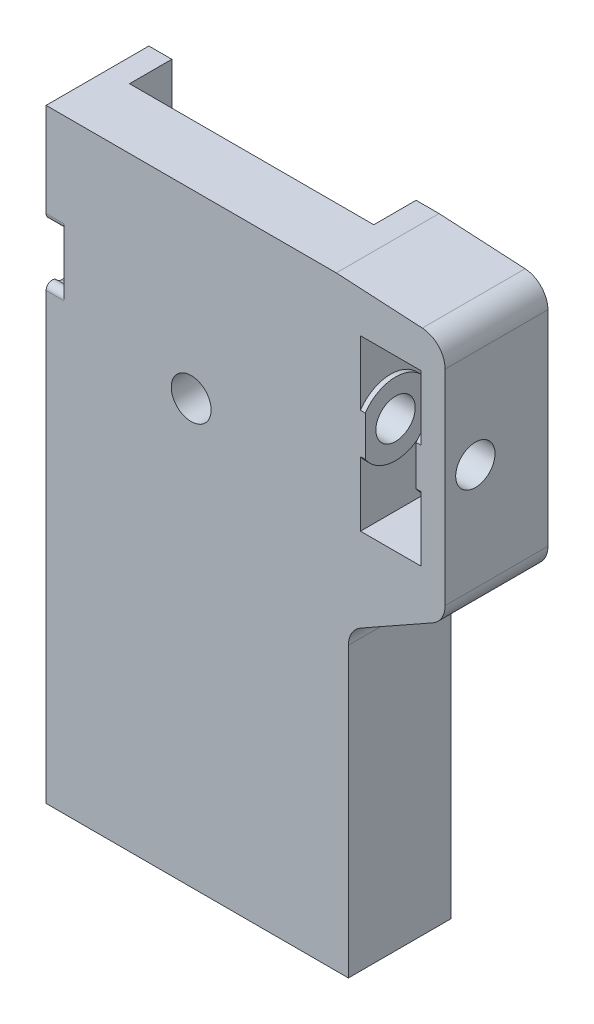
SolidWorks part; units mm, degrees
material "ABS"
ref_plane "前视基准面" through (0, 0, 0) normal (0, 0, 1) x (1, 0, 0)
ref_plane "上视基准面" through (0, 0, 0) normal (0, 1, 0) x (1, 0, 0)
ref_plane "右视基准面" through (0, 0, 0) normal (1, 0, 0) x (0, 0, -1)
other "Configuration Table"
sketch "草图1" plane through (0, 0, 0) normal (0, 0, 1) x (1, 0, 0)
  line L0 (33, 49.5) -> (24, 50)
  line L1 (24, 50) -> (0, 50)
  line L2 (0, 50) -> (0, 0)
  line L5 (33, 29.5) -> (33, 49.5)
  line L6 (26, 32.5) -> (31, 32.5)
  line L7 (26, 46.5) -> (26, 32.5)
  line L12 (31, 46.5) -> (26, 46.5)
  line L17 (31, 32.5) -> (31, 46.5)
  line L18 (0, 0) -> (25, 0)
  line L20 (25, 0) -> (33, 29.5) construction
  line L24 (0, 0) -> (25, 0)
  line L25 (33, 29.5) -> (33, 49.5)
  line L26 (33, 49.5) -> (24, 50)
  line L27 (33, 29.5) -> (25, 25)
  line L28 (25, 25) -> (25, 0)
  circle A0 centre (12, 35) radius 1.65
  dimension "D5" = 3.3
  dimension "D6" = 12
  dimension "D7" = 15
  dimension "D2" = 50
  dimension "D3" = 90
  dimension "D4" = 29.5
  dimension "D8" = 3.5
  dimension "D9" = 26
  dimension "D10" = 5
  dimension "D11" = 14
  dimension "D12" = 25
  dimension "D13" = 33
  dimension "D14" = 4.5
  dimension "D15" = 20
  dimension "D16" = 24
  dimension "D17" = 5
extrude "凸台-拉伸1" add sketch "草图1" against normal blind 8.5 contours L18 L20 L5 L0 L1 L2 A0 L17 L6 L7 L12 region at (13.8498, 25.9744, 0)
sketch "草图2" plane through (0, 50, 0) normal (0, 1, 0) x (1, 0, 0)
  line L0 (24, 8.5) -> (0, 8.5) construction
  line L1 (1.9, 8.5) -> (22.1, 8.5)
  line L2 (1.9, 8.5) -> (1.9, 5)
  line L3 (1.9, 5) -> (22.1, 5)
  line L4 (22.1, 8.5) -> (22.1, 5)
  line L5 (0, 8.5) -> (0, 0) construction
  dimension "D1" = 1.9
  dimension "D2" = 20.2
  dimension "D3" = 3.5
extrude "切除-拉伸1" cut sketch "草图2" against normal through all
sketch "草图3" plane through (33, 0, 0) normal (1, 0, 0) x (0, 0, -1)
  line L0 (0, 29.5) -> (0, 49.5) construction
  circle A0 centre (2.5, 39.5) radius 1.625
  dimension "D1" = 3.25
  dimension "D2" = 2.5
  dimension "D3" = 7
extrude "切除-拉伸2" cut sketch "草图3" against normal through all
sketch "草图6" plane through (31, 0, 0) normal (-1, 0, 0) x (0, 0, 1)
  line L0 (0, 32.5) -> (0, 46.5) construction
  line L1 (0, 37.8417) -> (0, 41.1583)
  circle A0 centre (-2.5, 39.5) radius 1.625 construction
  circle A1 centre (-2.5, 39.5) radius 1.625
  arc A2 (0, 41.1583) -> (0, 37.8417) centre (-2.5, 39.5) ccw
  dimension "D1" = 6
extrude "凸台-拉伸3" add sketch "草图6" along normal blind 0.4
fillet "圆角1" radius 2 3 edges at (33, 49.5, -4.25) (25, 25, -4.25) (33, 29.5, -4.25)
sketch "草图7" plane through (26, 0, 0) normal (1, 0, 0) x (0, 0, -1)
  line L1 (0, 41.1583) -> (0, 37.8417)
  line L2 (0, 41.1583) -> (0, 37.8417)
  circle A0 centre (2.5, 39.5) radius 1.625 construction
  arc A1 (0, 37.8417) -> (0, 41.1583) centre (2.5, 39.5) ccw
  arc A2 (0, 37.8417) -> (0, 41.1583) centre (2.5, 39.5) ccw
  circle A3 centre (2.5, 39.5) radius 1.625
  dimension "D1" = 0
extrude "凸台-拉伸4" add sketch "草图7" along normal blind 0.4
sketch "草图8" plane through (0, 0, -8.5) normal (0, 0, -1) x (-1, 0, 0)
  line L0 (-26, 32.5) -> (-31, 32.5) construction
  line L1 (-31, 32.5) -> (-26, 32.5)
  line L2 (-31, 32.5) -> (-31, 21.5507)
  line L3 (-31, 21.5507) -> (-26, 21.5507)
  line L4 (-26, 32.5) -> (-26, 21.5507)
extrude "切除-拉伸3" cut sketch "草图8" against normal blind 2
fillet "圆角2" radius 0.5 2 edges at (31, 28.375, -7.5) (26, 25.5624, -7.5)
fillet "圆角3" radius 1 4 edges at (25.9472, 25.6067, -6.5) (31.2476, 28.7983, -6.5) (26, 29.1652, -6.5) (31, 30.865, -6.5)
sketch "草图9" plane through (0, 0, 0) normal (-1, 0, 0) x (0, 0, 1)
  line L1 (0.5311, 39.5) -> (-0.9845, 42.125)
  line L2 (-0.9845, 42.125) -> (-4.0155, 42.125)
  line L3 (-4.0155, 42.125) -> (-5.5311, 39.5)
  line L4 (-5.5311, 39.5) -> (-4.0155, 36.875)
  line L5 (-4.0155, 36.875) -> (-0.9845, 36.875)
  line L6 (-0.9845, 36.875) -> (0.5311, 39.5)
  circle A0 centre (-2.5, 39.5) radius 2.625 construction
  dimension "D1" = 5.25
extrude "切除-拉伸4" cut sketch "草图9" against normal blind 1.5
fillet "圆角4" radius 0.5 5 edges at (0.75, 36.875, -0.9845) (0.75, 36.875, -4.0155) (0.75, 42.125, -4.0155) (0.75, 42.125, -0.9845) (0.75, 39.5, -5.5311)
fillet "圆角5" radius 0.5 2 edges at (0.75, 40.4199, 0) (0.75, 38.5801, 0)
